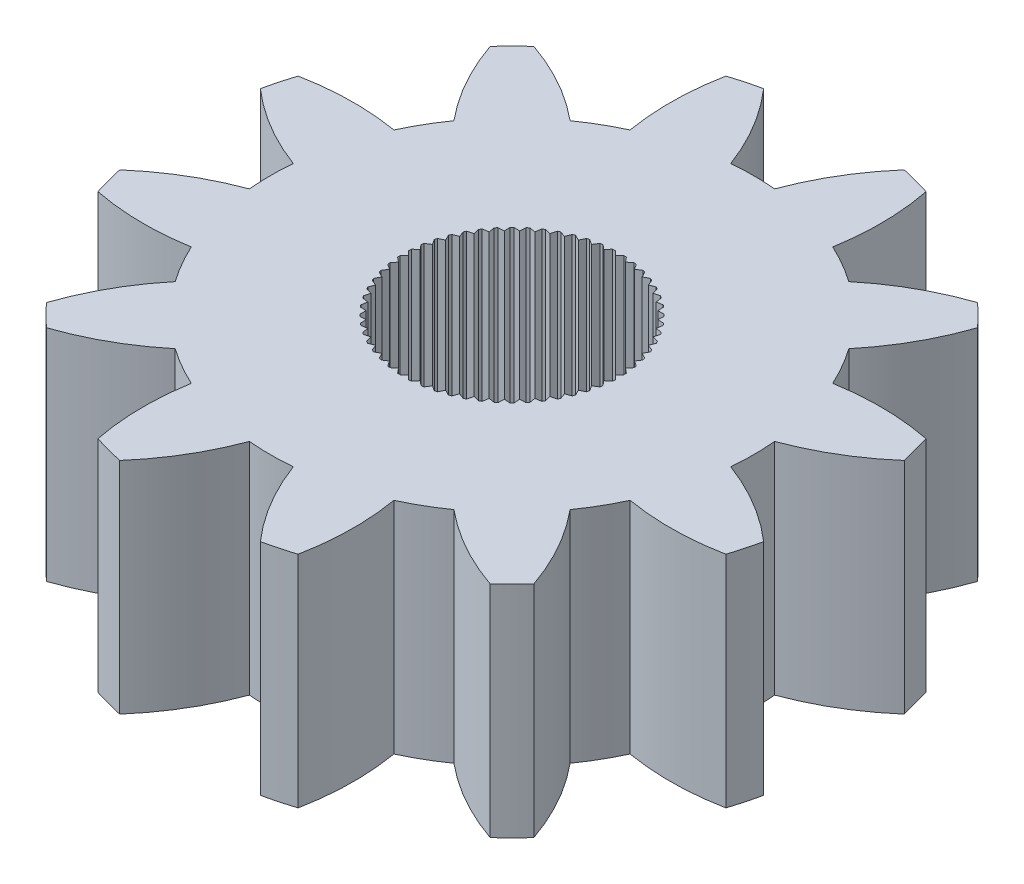
SolidWorks part; units mm, degrees
ref_plane "Front Plane" through (0, 0, 0) normal (0, 0, 1) x (1, 0, 0)
ref_plane "Top Plane" through (0, 0, 0) normal (0, 1, 0) x (1, 0, 0)
ref_plane "Right Plane" through (0, 0, 0) normal (1, 0, 0) x (0, 0, -1)
sketch "Croquis2" plane through (0, 0, 0) normal (0, 1, 0) x (1, 0, 0)
  line L0 (45, 0) -> (46.0553, 0) construction
  line L1 (-75, -40) -> (55, -40)
  line L2 (-75, -40) -> (-75, 40)
  line L3 (-75, 40) -> (55, 40)
  line L4 (75, -20) -> (75, 20)
  line L5 (45, 0) -> (46.0553, 0) construction
  line L6 (67, 26.7583) -> (67, -26.7583)
  line L7 (45, -30) -> (-50, -30)
  line L8 (45, -30) -> (45, 30)
  line L9 (45, 30) -> (-50, 30)
  line L10 (-50, -30) -> (-50, 30)
  line L11 (67, -26.7583) -> (67, 26.7583)
  line L13 (67, 26.7583) -> (61, 26.7583)
  line L15 (46.228, -1.6) -> (46.2586, -1.7343)
  line L16 (61.1553, 0) -> (61.0553, 0) construction
  line L17 (54.1602, 2.3742) -> (54.0439, 2.2986)
  line L18 (54.0439, 2.2986) -> (53.9684, 2.4149)
  line L19 (53.9087, 2.4244) -> (53.801, 2.3371)
  line L20 (53.801, 2.3371) -> (53.7137, 2.4449)
  line L21 (53.6534, 2.448) -> (53.5553, 2.35)
  line L22 (53.5553, 2.35) -> (53.4573, 2.448)
  line L23 (53.3969, 2.4449) -> (53.3097, 2.3371)
  line L24 (53.3097, 2.3371) -> (53.2019, 2.4244)
  line L25 (53.1422, 2.4149) -> (53.0667, 2.2986)
  line L26 (53.0667, 2.2986) -> (52.9505, 2.3742)
  line L27 (52.8921, 2.3585) -> (52.8291, 2.235)
  line L28 (52.8291, 2.235) -> (52.7056, 2.2979)
  line L29 (52.6492, 2.2763) -> (52.5995, 2.1468)
  line L30 (52.5995, 2.1468) -> (52.4701, 2.1965)
  line L31 (52.4162, 2.1691) -> (52.3803, 2.0352)
  line L32 (52.3803, 2.0352) -> (52.2464, 2.071)
  line L33 (52.1957, 2.0381) -> (52.174, 1.9012)
  line L34 (52.174, 1.9012) -> (52.0371, 1.9229)
  line L35 (51.9901, 1.8848) -> (51.9829, 1.7464)
  line L36 (51.9829, 1.7464) -> (51.8444, 1.7536)
  line L37 (51.8017, 1.7109) -> (51.8089, 1.5725)
  line L38 (51.8089, 1.5725) -> (51.6705, 1.5652)
  line L39 (51.6325, 1.5182) -> (51.6541, 1.3813)
  line L40 (51.6541, 1.3813) -> (51.5172, 1.3596)
  line L41 (51.4843, 1.3089) -> (51.5202, 1.175)
  line L42 (51.5202, 1.175) -> (51.3862, 1.1391)
  line L43 (51.3588, 1.0853) -> (51.4085, 0.9558)
  line L44 (51.4085, 0.9558) -> (51.2791, 0.9061)
  line L45 (51.2574, 0.8497) -> (51.3203, 0.7262)
  line L46 (51.3203, 0.7262) -> (51.1968, 0.6632)
  line L47 (51.1812, 0.6049) -> (51.2567, 0.4886)
  line L48 (51.2567, 0.4886) -> (51.1404, 0.4131)
  line L49 (51.1309, 0.3534) -> (51.2182, 0.2456)
  line L50 (51.2182, 0.2456) -> (51.1105, 0.1584)
  line L51 (51.1073, 0.098) -> (51.2053, 0)
  line L52 (51.2053, 0) -> (51.1073, -0.098)
  line L53 (51.1105, -0.1584) -> (51.2182, -0.2456)
  line L54 (51.2182, -0.2456) -> (51.1309, -0.3534)
  line L55 (51.1404, -0.4131) -> (51.2567, -0.4886)
  line L56 (51.2567, -0.4886) -> (51.1812, -0.6049)
  line L57 (51.1968, -0.6632) -> (51.3203, -0.7262)
  line L58 (51.3203, -0.7262) -> (51.2574, -0.8497)
  line L59 (51.2791, -0.9061) -> (51.4085, -0.9558)
  line L60 (51.4085, -0.9558) -> (51.3588, -1.0853)
  line L61 (51.3862, -1.1391) -> (51.5202, -1.175)
  line L62 (51.5202, -1.175) -> (51.4843, -1.3089)
  line L63 (51.5172, -1.3596) -> (51.6541, -1.3813)
  line L64 (51.6541, -1.3813) -> (51.6325, -1.5182)
  line L65 (51.6705, -1.5652) -> (51.8089, -1.5725)
  line L66 (51.8089, -1.5725) -> (51.8017, -1.7109)
  line L67 (51.8444, -1.7536) -> (51.9829, -1.7464)
  line L68 (51.9829, -1.7464) -> (51.9901, -1.8848)
  line L69 (52.0371, -1.9229) -> (52.174, -1.9012)
  line L70 (52.174, -1.9012) -> (52.1957, -2.0381)
  line L71 (52.2464, -2.071) -> (52.3803, -2.0352)
  line L72 (52.3803, -2.0352) -> (52.4162, -2.1691)
  line L73 (52.4701, -2.1965) -> (52.5995, -2.1468)
  line L74 (52.5995, -2.1468) -> (52.6492, -2.2763)
  line L75 (52.7056, -2.2979) -> (52.8291, -2.235)
  line L76 (52.8291, -2.235) -> (52.8921, -2.3585)
  line L77 (52.9505, -2.3742) -> (53.0667, -2.2986)
  line L78 (53.0667, -2.2986) -> (53.1422, -2.4149)
  line L79 (53.2019, -2.4244) -> (53.3097, -2.3371)
  line L80 (53.3097, -2.3371) -> (53.3969, -2.4449)
  line L81 (53.4573, -2.448) -> (53.5553, -2.35)
  line L82 (53.5553, -2.35) -> (53.6534, -2.448)
  line L83 (53.7137, -2.4449) -> (53.801, -2.3371)
  line L84 (53.801, -2.3371) -> (53.9087, -2.4244)
  line L85 (53.9684, -2.4149) -> (54.0439, -2.2986)
  line L86 (54.0439, -2.2986) -> (54.1602, -2.3742)
  line L87 (54.2186, -2.3585) -> (54.2815, -2.235)
  line L88 (54.2815, -2.235) -> (54.4051, -2.2979)
  line L89 (54.4615, -2.2763) -> (54.5112, -2.1468)
  line L90 (54.5112, -2.1468) -> (54.6406, -2.1965)
  line L91 (54.6944, -2.1691) -> (54.7303, -2.0352)
  line L92 (54.7303, -2.0352) -> (54.8643, -2.071)
  line L93 (54.9149, -2.0381) -> (54.9366, -1.9012)
  line L94 (54.9366, -1.9012) -> (55.0736, -1.9229)
  line L95 (55.1205, -1.8848) -> (55.1278, -1.7464)
  line L96 (55.1278, -1.7464) -> (55.2662, -1.7536)
  line L97 (55.309, -1.7109) -> (55.3017, -1.5725)
  line L98 (55.3017, -1.5725) -> (55.4402, -1.5652)
  line L99 (55.4782, -1.5182) -> (55.4565, -1.3813)
  line L100 (55.4565, -1.3813) -> (55.5935, -1.3596)
  line L101 (55.6264, -1.3089) -> (55.5905, -1.175)
  line L102 (55.5905, -1.175) -> (55.7244, -1.1391)
  line L103 (55.7518, -1.0853) -> (55.7022, -0.9558)
  line L104 (55.7022, -0.9558) -> (55.8316, -0.9061)
  line L105 (55.8533, -0.8497) -> (55.7903, -0.7262)
  line L106 (55.7903, -0.7262) -> (55.9138, -0.6632)
  line L107 (55.9295, -0.6049) -> (55.854, -0.4886)
  line L108 (55.854, -0.4886) -> (55.9703, -0.4131)
  line L109 (55.9797, -0.3534) -> (55.8925, -0.2456)
  line L110 (55.8925, -0.2456) -> (56.0002, -0.1584)
  line L111 (56.0034, -0.098) -> (55.9053, 0)
  line L112 (55.9053, 0) -> (56.0034, 0.098)
  line L113 (56.0002, 0.1584) -> (55.8925, 0.2456)
  line L114 (55.8925, 0.2456) -> (55.9797, 0.3534)
  line L115 (55.9703, 0.4131) -> (55.854, 0.4886)
  line L116 (55.854, 0.4886) -> (55.9295, 0.6049)
  line L117 (55.9138, 0.6632) -> (55.7903, 0.7262)
  line L118 (55.7903, 0.7262) -> (55.8533, 0.8497)
  line L119 (55.8316, 0.9061) -> (55.7022, 0.9558)
  line L120 (55.7022, 0.9558) -> (55.7518, 1.0853)
  line L121 (55.7244, 1.1391) -> (55.5905, 1.175)
  line L122 (55.5905, 1.175) -> (55.6264, 1.3089)
  line L123 (55.5935, 1.3596) -> (55.4565, 1.3813)
  line L124 (55.4565, 1.3813) -> (55.4782, 1.5182)
  line L125 (55.4402, 1.5652) -> (55.3017, 1.5725)
  line L126 (55.3017, 1.5725) -> (55.309, 1.7109)
  line L127 (55.2662, 1.7536) -> (55.1278, 1.7464)
  line L128 (55.1278, 1.7464) -> (55.1205, 1.8848)
  line L129 (55.0736, 1.9229) -> (54.9366, 1.9012)
  line L130 (54.9366, 1.9012) -> (54.9149, 2.0381)
  line L131 (54.8643, 2.071) -> (54.7303, 2.0352)
  line L132 (54.7303, 2.0352) -> (54.6944, 2.1691)
  line L133 (54.6406, 2.1965) -> (54.5112, 2.1468)
  line L134 (54.5112, 2.1468) -> (54.4615, 2.2763)
  line L135 (54.4051, 2.2979) -> (54.2815, 2.235)
  line L136 (54.2815, 2.235) -> (54.2186, 2.3585)
  line L137 (53.5553, 0) -> (53.5553, -7.5) construction
  line L139 (65.0006, 25.8237) -> (59.5501, 25.8237) construction
  line L141 (61.0553, 0) -> (67, 0) construction
  line L142 (59.0553, 0) -> (53.5553, 0) construction
  line L143 (48.0553, 0) -> (53.5553, 0) construction
  line L144 (48.0553, 0) -> (59.0553, 0) construction
  line L145 (60.701, 2.278) -> (60.8827, 1.6)
  line L146 (61, 24.889) -> (61, 23.889)
  line L149 (61, 22.0197) -> (61, 21.0197)
  line L152 (61, 19.1504) -> (61, 18.1504)
  line L154 (59.5501, 17.5667) -> (59.5501, 16.8648)
  line L155 (61, 16.2811) -> (61, 15.2811)
  line L157 (59.5501, 14.6974) -> (59.5501, 13.9955)
  line L158 (61, 13.4118) -> (61, 12.4118)
  line L160 (59.5501, 11.8282) -> (59.5501, 11.1262)
  line L161 (61, 10.5425) -> (61, 9.5425)
  line L163 (59.5501, 8.9589) -> (59.5501, 8.2569)
  line L164 (61, 7.6732) -> (61, 6.6732)
  line L166 (59.5501, 6.0896) -> (59.5501, 5.3876)
  line L167 (61, 4.8039) -> (61, 3.8039)
  line L169 (59.5501, 3.2203) -> (59.5501, 2.5183)
  line L170 (61, 1.9346) -> (61, 0.9346)
  line L172 (59.5501, 0.351) -> (59.5501, -0.351)
  line L173 (61, -0.9346) -> (61, -1.9346)
  line L175 (59.5501, -2.5183) -> (59.5501, -3.2203)
  line L176 (61, -3.8039) -> (61, -4.8039)
  line L178 (59.5501, -5.3876) -> (59.5501, -6.0896)
  line L179 (61, -6.6732) -> (61, -7.6732)
  line L181 (59.5501, -8.2569) -> (59.5501, -8.9589)
  line L182 (61, -9.5425) -> (61, -10.5425)
  line L184 (59.5501, -11.1262) -> (59.5501, -11.8282)
  line L185 (61, -12.4118) -> (61, -13.4118)
  line L187 (59.5501, -13.9955) -> (59.5501, -14.6974)
  line L188 (61, -15.2811) -> (61, -16.2811)
  line L190 (59.5501, -16.8648) -> (59.5501, -17.5667)
  line L191 (61, -18.1504) -> (61, -19.1504)
  line L194 (61, -21.0197) -> (61, -22.0197)
  line L197 (61, -23.889) -> (61, -24.889)
  line L200 (64, 26.7583) -> (64, 26.3977) construction
  line L203 (61, -26.7583) -> (67, -26.7583)
  line L204 (75, 20) -> (67, 20) construction
  line L205 (61, -26.7583) -> (61, -27.7583) [skipped]
  line L206 (-50, 0) -> (-75, 0) construction
  line L207 (75, -20) -> (67, -20) construction
  line L208 (50, -40) -> (50, 40) construction
  line L209 (50, -35) -> (50, -43.5216) construction
  line L210 (53.5731, -35) -> (53.5731, -43.5216)
  line L211 (46.4269, -35) -> (46.4269, -43.5216)
  line L212 (50.0036, 34.1275) -> (50.0036, 40.0656) construction
  line L213 (53.6852, 34.1275) -> (53.5731, 43.5216)
  line L214 (46.4269, 35) -> (46.4269, 43.5216)
  line L215 (-50, -30) -> (-47.1716, -27.1716) construction
  line L221 (-50, -30) -> (-47.1716, -30)
  line L222 (-50, -30) -> (-50, -27.1716)
  line L223 (46.4269, -43.5216) -> (46.4269, -48.5216)
  line L224 (53.5731, -43.5216) -> (53.5731, -48.5216)
  line L225 (46.4269, -48.5216) -> (53.5731, -48.5216)
  line L226 (53.5731, 43.5216) -> (53.5731, 48.5216)
  line L227 (46.4269, 43.5216) -> (46.4269, 48.5216)
  line L228 (46.4269, 48.5216) -> (53.5731, 48.5216)
  line L229 (50, 43.0304) -> (64, 23.3977) construction
  line L232 (46.4269, 48.5216) -> (53.5731, 48.5216)
  line L233 (46.4269, 48.5216) -> (46.4269, 46.5216)
  line L234 (53.5731, 48.5216) -> (53.5731, 46.5216)
  line L235 (46.4269, 46.5216) -> (53.5731, 46.5216)
  line L236 (46.4269, -46.5216) -> (53.5731, -46.5216)
  line L239 (61, 19.1504) -> (67, 19.1504)
  line L240 (61, 26.7583) -> (61, 19.1504)
  line L241 (50.0036, 40.0656) -> (61.1732, 24.4022)
  line L242 (52.8363, 42.0529) -> (64, 26.3977)
  line L243 (48.6009, 42.0327) -> (62.6009, 22.4) construction
  line L244 (51.4182, 44.0416) -> (65.4182, 24.409) construction
  line L245 (61, 24.889) -> (61, 26.7583)
  line L246 (64, 25.8237) -> (64, -26.7583) construction
  line L248 (-70.5, -35) -> (-54.5, -35)
  line L249 (61, -26.7583) -> (61, -19.1504)
  line L250 (61, -19.1504) -> (67, -19.1504)
  line L251 (-50, -27.1716) -> (-47.1716, -27.1716)
  line L252 (-47.1716, -30) -> (-47.1716, -27.1716)
  line L253 (-2.5, -30) -> (-2.5, 30) construction
  line L254 (-70.5, -35) -> (-70.5, -40)
  line L255 (-54.5, 35) -> (-70.5, 35)
  line L260 (-54.5, 35) -> (-54.5, -35)
  line L261 (-54.5, -35) -> (-70.5, -35)
  line L262 (-70.5, 35) -> (-70.5, -35)
  line L263 (-54.5, 35) -> (-70.5, -35) construction
  line L264 (-54.5, -35) -> (-70.5, 35) construction
  line L265 (-70.5, -40) -> (-54.5, -40)
  line L266 (-54.5, -35) -> (-54.5, -40)
  line L267 (-70.5, 35) -> (-54.5, 35)
  line L268 (-70.5, 35) -> (-70.5, 40)
  line L269 (-70.5, 40) -> (-54.5, 40)
  line L270 (-54.5, 35) -> (-54.5, 40)
  circle A0 centre (53.5553, 0) radius 7.5
  arc A1 (53.9684, 2.4149) -> (53.9087, 2.4244) centre (53.5553, 0) ccw
  arc A2 (53.7137, 2.4449) -> (53.6534, 2.448) centre (53.5553, 0) ccw
  arc A3 (53.4573, 2.448) -> (53.3969, 2.4449) centre (53.5553, 0) ccw
  arc A4 (53.2019, 2.4244) -> (53.1422, 2.4149) centre (53.5553, 0) ccw
  arc A5 (52.9505, 2.3742) -> (52.8921, 2.3585) centre (53.5553, 0) ccw
  arc A6 (52.7056, 2.2979) -> (52.6492, 2.2763) centre (53.5553, 0) ccw
  arc A7 (52.4701, 2.1965) -> (52.4162, 2.1691) centre (53.5553, 0) ccw
  arc A8 (52.2464, 2.071) -> (52.1957, 2.0381) centre (53.5553, 0) ccw
  arc A9 (52.0371, 1.9229) -> (51.9901, 1.8848) centre (53.5553, 0) ccw
  arc A10 (51.8444, 1.7536) -> (51.8017, 1.7109) centre (53.5553, 0) ccw
  arc A11 (51.6705, 1.5652) -> (51.6325, 1.5182) centre (53.5553, 0) ccw
  arc A12 (51.5172, 1.3596) -> (51.4843, 1.3089) centre (53.5553, 0) ccw
  arc A13 (51.3862, 1.1391) -> (51.3588, 1.0853) centre (53.5553, 0) ccw
  arc A14 (51.2791, 0.9061) -> (51.2574, 0.8497) centre (53.5553, 0) ccw
  arc A15 (51.1968, 0.6632) -> (51.1812, 0.6049) centre (53.5553, 0) ccw
  arc A16 (51.1404, 0.4131) -> (51.1309, 0.3534) centre (53.5553, 0) ccw
  arc A17 (51.1105, 0.1584) -> (51.1073, 0.098) centre (53.5553, 0) ccw
  arc A18 (51.1073, -0.098) -> (51.1105, -0.1584) centre (53.5553, 0) ccw
  arc A19 (51.1309, -0.3534) -> (51.1404, -0.4131) centre (53.5553, 0) ccw
  arc A20 (51.1812, -0.6049) -> (51.1968, -0.6632) centre (53.5553, 0) ccw
  arc A21 (51.2574, -0.8497) -> (51.2791, -0.9061) centre (53.5553, 0) ccw
  arc A22 (51.3588, -1.0853) -> (51.3862, -1.1391) centre (53.5553, 0) ccw
  arc A23 (51.4843, -1.3089) -> (51.5172, -1.3596) centre (53.5553, 0) ccw
  arc A24 (51.6325, -1.5182) -> (51.6705, -1.5652) centre (53.5553, 0) ccw
  arc A25 (51.8017, -1.7109) -> (51.8444, -1.7536) centre (53.5553, 0) ccw
  arc A26 (51.9901, -1.8848) -> (52.0371, -1.9229) centre (53.5553, 0) ccw
  arc A27 (52.1957, -2.0381) -> (52.2464, -2.071) centre (53.5553, 0) ccw
  arc A28 (52.4162, -2.1691) -> (52.4701, -2.1965) centre (53.5553, 0) ccw
  arc A29 (52.6492, -2.2763) -> (52.7056, -2.2979) centre (53.5553, 0) ccw
  arc A30 (52.8921, -2.3585) -> (52.9505, -2.3742) centre (53.5553, 0) ccw
  arc A31 (53.1422, -2.4149) -> (53.2019, -2.4244) centre (53.5553, 0) ccw
  arc A32 (53.3969, -2.4449) -> (53.4573, -2.448) centre (53.5553, 0) ccw
  arc A33 (53.6534, -2.448) -> (53.7137, -2.4449) centre (53.5553, 0) ccw
  arc A34 (53.9087, -2.4244) -> (53.9684, -2.4149) centre (53.5553, 0) ccw
  arc A35 (54.1602, -2.3742) -> (54.2186, -2.3585) centre (53.5553, 0) ccw
  arc A36 (54.4051, -2.2979) -> (54.4615, -2.2763) centre (53.5553, 0) ccw
  arc A37 (54.6406, -2.1965) -> (54.6944, -2.1691) centre (53.5553, 0) ccw
  arc A38 (54.8643, -2.071) -> (54.9149, -2.0381) centre (53.5553, 0) ccw
  arc A39 (55.0736, -1.9229) -> (55.1205, -1.8848) centre (53.5553, 0) ccw
  arc A40 (55.2662, -1.7536) -> (55.309, -1.7109) centre (53.5553, 0) ccw
  arc A41 (55.4402, -1.5652) -> (55.4782, -1.5182) centre (53.5553, 0) ccw
  arc A42 (55.5935, -1.3596) -> (55.6264, -1.3089) centre (53.5553, 0) ccw
  arc A43 (55.7244, -1.1391) -> (55.7518, -1.0853) centre (53.5553, 0) ccw
  arc A44 (55.8316, -0.9061) -> (55.8533, -0.8497) centre (53.5553, 0) ccw
  arc A45 (55.9138, -0.6632) -> (55.9295, -0.6049) centre (53.5553, 0) ccw
  arc A46 (55.9703, -0.4131) -> (55.9797, -0.3534) centre (53.5553, 0) ccw
  arc A47 (56.0002, -0.1584) -> (56.0034, -0.098) centre (53.5553, 0) ccw
  arc A48 (56.0034, 0.098) -> (56.0002, 0.1584) centre (53.5553, 0) ccw
  arc A49 (55.9797, 0.3534) -> (55.9703, 0.4131) centre (53.5553, 0) ccw
  arc A50 (55.9295, 0.6049) -> (55.9138, 0.6632) centre (53.5553, 0) ccw
  arc A51 (55.8533, 0.8497) -> (55.8316, 0.9061) centre (53.5553, 0) ccw
  arc A52 (55.7518, 1.0853) -> (55.7244, 1.1391) centre (53.5553, 0) ccw
  arc A53 (55.6264, 1.3089) -> (55.5935, 1.3596) centre (53.5553, 0) ccw
  arc A54 (55.4782, 1.5182) -> (55.4402, 1.5652) centre (53.5553, 0) ccw
  arc A55 (55.309, 1.7109) -> (55.2662, 1.7536) centre (53.5553, 0) ccw
  arc A56 (55.1205, 1.8848) -> (55.0736, 1.9229) centre (53.5553, 0) ccw
  arc A57 (54.9149, 2.0381) -> (54.8643, 2.071) centre (53.5553, 0) ccw
  arc A58 (54.6944, 2.1691) -> (54.6406, 2.1965) centre (53.5553, 0) ccw
  arc A59 (54.4615, 2.2763) -> (54.4051, 2.2979) centre (53.5553, 0) ccw
  arc A60 (54.2186, 2.3585) -> (54.1602, 2.3742) centre (53.5553, 0) ccw
  circle A61 centre (53.5553, 0) radius 2.25
  arc A62 (55, 40) -> (75, 20) centre (55, 20) cw
  arc A63 (55, -40) -> (75, -20) centre (55, -20) ccw
  circle A64 centre (53.5553, 0) radius 5.5
  arc A65 (54.0553, -5.4772) -> (55.1553, -7.3273) centre (59.6317, -3.4139) ccw
  arc A66 (53.0553, -5.4772) -> (51.9553, -7.3273) centre (47.479, -3.4139) cw
  arc A67 (50.3837, -4.4934) -> (48.506, -5.5457) centre (46.5861, 0.0817) cw
  arc A68 (51.2497, -4.9934) -> (51.2773, -7.1457) centre (57.1107, -5.9946) ccw
  arc A69 (48.5619, -2.3056) -> (46.4097, -2.278) centre (47.5607, 3.5553) cw
  arc A70 (49.0619, -3.1716) -> (48.0097, -5.0493) centre (53.637, -6.9692) ccw
  arc A71 (48.0781, 0.5) -> (46.228, 1.6) centre (50.1415, 6.0763) cw
  arc A72 (48.0781, -0.5) -> (46.228, -1.6) centre (50.1415, -6.0763) ccw
  arc A73 (49.0619, 3.1716) -> (48.0097, 5.0493) centre (53.637, 6.9692) cw
  arc A74 (48.5619, 2.3056) -> (46.4097, 2.278) centre (47.5607, -3.5553) ccw
  arc A75 (51.2497, 4.9934) -> (51.2773, 7.1457) centre (57.1107, 5.9946) cw
  arc A76 (50.3837, 4.4934) -> (48.506, 5.5457) centre (46.5861, -0.0817) ccw
  arc A77 (54.0553, 5.4772) -> (55.1553, 7.3273) centre (59.6317, 3.4139) cw
  arc A78 (53.0553, 5.4772) -> (51.9553, 7.3273) centre (47.479, 3.4139) ccw
  arc A79 (56.727, 4.4934) -> (58.6046, 5.5457) centre (60.5245, -0.0817) cw
  arc A80 (55.8609, 4.9934) -> (55.8334, 7.1457) centre (50, 5.9946) ccw
  arc A81 (58.5487, 2.3056) -> (60.701, 2.278) centre (59.55, -3.5553) cw
  arc A82 (58.0487, 3.1716) -> (59.101, 5.0493) centre (53.4736, 6.9692) ccw
  arc A83 (59.0326, -0.5) -> (60.8827, -1.6) centre (56.9692, -6.0763) cw
  arc A84 (59.0326, 0.5) -> (60.8827, 1.6) centre (56.9692, 6.0763) ccw
  arc A85 (58.0487, -3.1716) -> (59.101, -5.0493) centre (53.4736, -6.9692) cw
  arc A86 (58.5487, -2.3056) -> (60.701, -2.278) centre (59.55, 3.5553) ccw
  arc A89 (55.8609, -4.9934) -> (55.8334, -7.1457) centre (50, -5.9946) cw
  arc A90 (56.727, -4.4934) -> (58.6046, -5.5457) centre (60.5245, 0.0817) ccw
  arc A95 (61, 16.2811) -> (59.5501, 16.8648) centre (62.2327, 21.4358) cw
  arc A96 (61, 18.1504) -> (59.5501, 17.5667) centre (62.2327, 12.9958) ccw
  arc A97 (61, 13.4118) -> (59.5501, 13.9955) centre (62.2327, 18.5665) cw
  arc A98 (61, 15.2811) -> (59.5501, 14.6974) centre (62.2327, 10.1265) ccw
  arc A99 (61, 10.5425) -> (59.5501, 11.1262) centre (62.2327, 15.6972) cw
  arc A100 (61, 12.4118) -> (59.5501, 11.8282) centre (62.2327, 7.2572) ccw
  arc A101 (61, 7.6732) -> (59.5501, 8.2569) centre (62.2327, 12.8279) cw
  arc A102 (61, 9.5425) -> (59.5501, 8.9589) centre (62.2327, 4.3879) ccw
  arc A103 (61, 4.8039) -> (59.5501, 5.3876) centre (62.2327, 9.9586) cw
  arc A104 (61, 6.6732) -> (59.5501, 6.0896) centre (62.2327, 1.5186) ccw
  arc A105 (61, 1.9346) -> (59.5501, 2.5183) centre (62.2327, 7.0893) cw
  arc A106 (61, 3.8039) -> (59.5501, 3.2203) centre (62.2327, -1.3507) ccw
  arc A107 (61, -0.9346) -> (59.5501, -0.351) centre (62.2327, 4.22) cw
  arc A108 (61, 0.9346) -> (59.5501, 0.351) centre (62.2327, -4.22) ccw
  arc A109 (61, -3.8039) -> (59.5501, -3.2203) centre (62.2327, 1.3507) cw
  arc A110 (61, -1.9346) -> (59.5501, -2.5183) centre (62.2327, -7.0893) ccw
  arc A111 (61, -6.6732) -> (59.5501, -6.0896) centre (62.2327, -1.5186) cw
  arc A112 (61, -4.8039) -> (59.5501, -5.3876) centre (62.2327, -9.9586) ccw
  arc A113 (61, -9.5425) -> (59.5501, -8.9589) centre (62.2327, -4.3879) cw
  arc A114 (61, -7.6732) -> (59.5501, -8.2569) centre (62.2327, -12.8279) ccw
  arc A115 (61, -12.4118) -> (59.5501, -11.8282) centre (62.2327, -7.2572) cw
  arc A116 (61, -10.5425) -> (59.5501, -11.1262) centre (62.2327, -15.6972) ccw
  arc A117 (61, -15.2811) -> (59.5501, -14.6974) centre (62.2327, -10.1265) cw
  arc A118 (61, -13.4118) -> (59.5501, -13.9955) centre (62.2327, -18.5665) ccw
  arc A119 (61, -18.1504) -> (59.5501, -17.5667) centre (62.2327, -12.9958) cw
  arc A120 (61, -16.2811) -> (59.5501, -16.8648) centre (62.2327, -21.4358) ccw
  circle A128 centre (64, -23.889) radius 1.5875
  circle A129 centre (64, 23.3977) radius 1.5875
  circle A130 centre (69.4482, 20) radius 2.175
  circle A131 centre (69.4482, -20) radius 2.175
  circle A132 centre (50, -35) radius 1.5875
  circle A133 centre (50.0036, 34.1275) radius 1.5875
  arc A134 (53.5731, -35) -> (46.4269, -35) centre (50, -35) ccw
  arc A136 (53.6852, 34.1275) -> (46.4269, 35) centre (50.0036, 34.1275) cw
  circle A138 centre (50, 43.0304) radius 1.7203
  circle A139 centre (50, -43.5216) radius 1.7203
  arc A142 (52.4426, 44.7721) -> (47.5574, 41.2886) centre (50, 43.0304) ccw
  arc A143 (61.5574, 21.6559) -> (66.4426, 25.1395) centre (64, 23.3977) ccw
  arc A144 (52.8363, 42.0529) -> (50.0286, 40.0305) centre (50, 43.0304) ccw
  arc A145 (61.1732, 24.4022) -> (64, 26.3977) centre (64, 23.3977) ccw
  arc A146 (62.2582, 25.8403) -> (62.2351, 25.8237) centre (64, 23.3977) ccw
  circle A151 centre (-47.1716, -27.1716) radius 2
  circle A152 centre (42.1716, -27.1716) radius 2
  circle A153 centre (42.1716, 27.1716) radius 2
  circle A154 centre (-47.1716, 27.1716) radius 2
  point P5 (65.0006, 25.8237)
  point P6 (0, 0)
  point P13 (67, 0)
  point P20 (59.8563, -29.3308)
  point P216 (53.5553, -7.5)
  point P221 (53.5553, -5.5)
  point P283 (53.5553, 0)
  point P290 (59.5501, 25.8237)
  point P292 (61, 24.889)
  point P297 (53.5553, 0)
  point P409 (-62.5, 0)
  point P411 (-62.5, 0)
  point P415 (-62.5, 0)
  point P424 (50, -39.2608)
  point P434 (50, 39.2608)
  point P453 (57, 33.214)
  dimension "D6" = 15
  dimension "D9" = 6
  dimension "D10" = 11
  dimension "D13" = 30
  dimension "D20" = 1
  dimension "D22" = 3.175
  dimension "D23" = 3.175
  dimension "D8" = 4.35
  dimension "D25" = 3.175
  dimension "D30" = 5
  dimension "D32" = 3
  dimension "D18" = 4
  dimension "D2" = 80
  dimension "D3" = 30
  dimension "D4" = 60
  dimension "D5" = 12
  dimension "D7" = 8.5553
  dimension "D11" = 0.5
  dimension "D12" = 1.6
  dimension "D14" = 4
  dimension "D15" = 95
  dimension "2.25" = 22
  dimension "D16" = 1.8693
  dimension "D17" = 1.8693
  dimension "D19" = 0.702
  dimension "D24" = 16
  dimension "D26" = 5
  dimension "D27" = 5
  dimension "D28" = 130
  dimension "D31" = 2
  dimension "D21" = 19
extrude "Saliente-Extruir1" add sketch "Croquis2" against normal blind 5 contours A64 A60 L136 L135 A59 L134 L133 A58 L132 L131 A57 L130 L129 A56 L128 L127 A55 L126 L125 A54 L124 L123 A53 L122 L121 A52 L120 | A64 A78 A0 A75 | A64 A80 A0 A77 | A64 A82 A0 A79 | L145 A105 A81 A64 A84 | A64 A90 A0 A85 | A89 A64 A65 A0 | A64 A68 A0 A66 | A64 A70 A0 A67 | A64 A72 L15 A0 A69 | A64 A74 A0 A71 | A64 A76 A0 A73 | A110 A0 A83 A64 A86 | A0 A110 A86 | A105 L145 A81 region at (60.3932, 0, -2.2225) region at (58.0433, 0, -4.488) region at (58.0433, 0, 4.488) region at (60.3966, 0, 2.2213) region at (59.6436, 0, -1.6088) region at (58.1837, 0, -2.6722) region at (59.6447, 0, 1.609) region at (55.1981, 0, -6.1307) region at (55.1981, 0, 6.1307) region at (51.9126, 0, -6.1307) region at (51.9126, 0, 6.1307) region at (49.0673, 0, -4.488) region at (49.0673, 0, 4.488) region at (47.4246, 0, -1.6427) region at (47.4246, 0, 1.6427)
sketch "Croquis3" plane through (0, 0, 0) normal (0, 1, 0) x (1, 0, 0)
  circle A0 centre (53.5553, 0) radius 7.5
